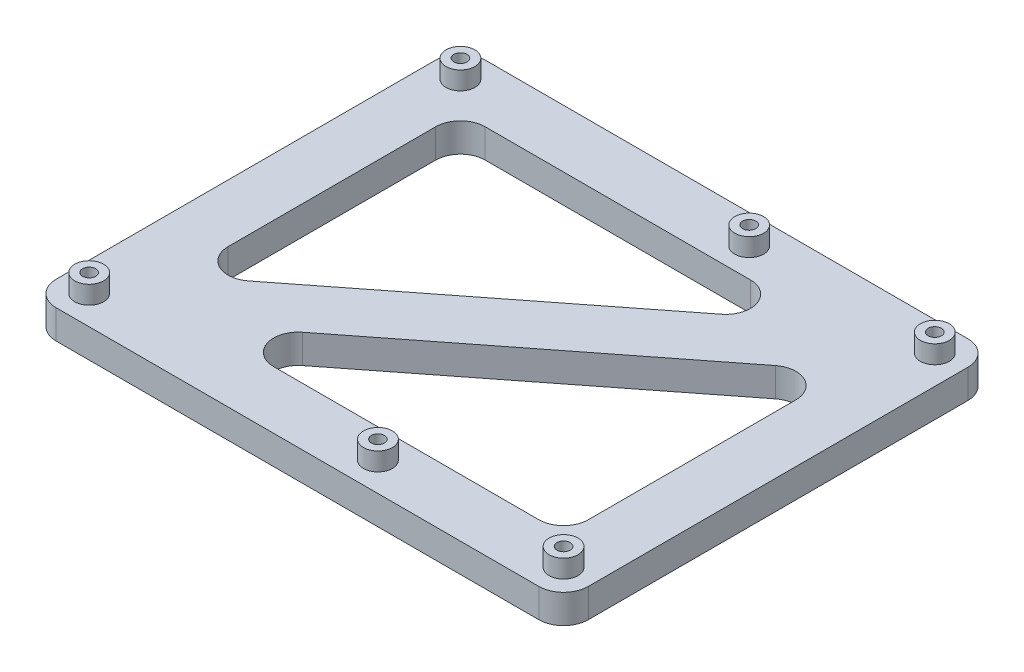
SolidWorks part; units mm, degrees
ref_plane "Front Plane" through (0, 0, 0) normal (0, 0, 1) x (1, 0, 0)
ref_plane "Top Plane" through (0, 0, 0) normal (0, 1, 0) x (1, 0, 0)
ref_plane "Right Plane" through (0, 0, 0) normal (1, 0, 0) x (0, 0, -1)
sketch "Sketch1" plane through (0, 0, 0) normal (0, 1, 0) x (1, 0, 0)
  line L0 (12.5, -45) -> (12.5, 45) construction
  line L1 (57.5, -45) -> (-57.5, -45) construction
  line L2 (57.5, -45) -> (57.5, 45) construction
  line L3 (57.5, 45) -> (-57.5, 45) construction
  line L4 (-57.5, -45) -> (-57.5, 45) construction
  line L5 (57.5, -45) -> (-57.5, 45) construction
  line L6 (57.5, 45) -> (-57.5, -45) construction
  line L7 (-50.5, -30.6329) -> (-50.5, 38)
  line L8 (50.5, 38) -> (48.5556, 38) construction
  line L9 (50.5, -38) -> (50.5, 30.6329)
  line L10 (50.5, -38) -> (-37.1976, -38)
  line L11 (-64.5, -52) -> (-64.5, 52)
  line L12 (64.5, 52) -> (-64.5, 52)
  line L13 (64.5, -52) -> (64.5, 52)
  line L14 (64.5, -52) -> (-64.5, -52)
  line L15 (53.1858, 50.5125) -> (46.142, 45) construction
  line L16 (61.8142, 39.4875) -> (57.5, 36.1112) construction
  line L17 (-57.5, -36.1112) -> (-61.8142, -39.4875) construction
  line L18 (53.1858, 50.5125) -> (-61.8142, -39.4875) construction
  line L19 (-50.5, -30.6329) -> (-57.5, -36.1112) construction
  line L20 (-46.142, -45) -> (-53.1858, -50.5125) construction
  line L21 (61.8142, 39.4875) -> (-53.1858, -50.5125) construction
  line L22 (-37.1976, -38) -> (-46.142, -45) construction
  line L23 (46.142, 45) -> (37.1976, 38) construction
  line L24 (37.1976, 38) -> (-50.5, -30.6329)
  line L25 (57.5, 36.1112) -> (50.5, 30.6329) construction
  line L26 (50.5, 30.6329) -> (-37.1976, -38)
  line L27 (-50.5, -38) -> (-50.5, -30.6329) construction
  line L28 (-50.5, -38) -> (-50.5, 38) construction
  line L29 (-48.5556, -38) -> (-50.5, -38) construction
  line L30 (50.5, -38) -> (-50.5, -38) construction
  line L31 (-37.1976, -38) -> (-48.5556, -38) construction
  line L32 (48.5556, 38) -> (37.1976, 38) construction
  line L33 (37.1976, 38) -> (-50.5, 38)
  line L34 (50.5, 38) -> (-50.5, 38) construction
  line L35 (50.5, 30.6329) -> (50.5, 38) construction
  line L36 (50.5, -38) -> (50.5, 38) construction
  circle A0 centre (12.5, 45) radius 1.6
  circle A1 centre (12.5, -45) radius 1.6
  circle A2 centre (-57.5, 45) radius 1.6
  circle A3 centre (-57.5, -45) radius 1.6
  circle A4 centre (57.5, -45) radius 1.6
  circle A5 centre (57.5, 45) radius 1.6
  circle A6 centre (-57.5, 45) radius 3.5
  circle A7 centre (12.5, 45) radius 3.5
  circle A8 centre (57.5, 45) radius 3.5
  circle A9 centre (-57.5, -45) radius 3.5
  circle A10 centre (12.5, -45) radius 3.5
  circle A11 centre (57.5, -45) radius 3.5
  point P0 (0, 0)
  dimension "D4" = 3.2
  dimension "D9" = 7
  dimension "D1" = 70
  dimension "D2" = 45
  dimension "D3" = 90
  dimension "D5" = 7
  dimension "D6" = 7
  dimension "D7" = 7
  dimension "D8" = 7
extrude "Boss-Extrude1" add sketch "Sketch1" along normal blind 7 contours L14 L13 L12 L11 A11 A10 A9 A8 A7 A6 L33 L24 L7 L26 L9 L10 region at (-0.1343, 0, 0)
fillet "Fillet1" radius 6 10 edges at (-64.5, 3.5, -52) (64.5, 3.5, -52) (64.5, 3.5, 52) (-37.1976, 3.5, 38) (50.5, 3.5, 38) (50.5, 3.5, -30.6329) (-50.5, 3.5, 30.6329) (37.1976, 3.5, -38) (-64.5, 3.5, 52) (-50.5, 3.5, -38)
extrude "Boss-Extrude2" add sketch "Sketch1<3>" along normal blind 11.4 contours A9 A3 | A6 A2 | A7 A0 | A8 A5 | A10 A1 | A11 A4 region at (-60.901, 0, -45) region at (9.099, 0, -45) region at (54.099, 0, -45) region at (-60.901, 0, 45) region at (9.099, 0, 45) region at (54.099, 0, 45)
sketch "Sketch1<3>" plane through (0, 0, 0) normal (0, 1, 0) x (1, 0, 0) same geometry as "Sketch1"
sketch "Sketch2" plane through (0, 0, 0) normal (0, -1, 0) x (1, 0, 0)
  line L1 (-54.3246, 45) -> (-55.9123, 47.75)
  line L2 (-55.9123, 47.75) -> (-59.0877, 47.75)
  line L3 (-59.0877, 47.75) -> (-60.6754, 45)
  line L4 (-60.6754, 45) -> (-59.0877, 42.25)
  line L5 (-59.0877, 42.25) -> (-55.9123, 42.25)
  line L6 (-55.9123, 42.25) -> (-54.3246, 45)
  line L7 (15.6754, 45) -> (14.0877, 47.75)
  line L8 (14.0877, 47.75) -> (10.9123, 47.75)
  line L9 (10.9123, 47.75) -> (9.3246, 45)
  line L10 (9.3246, 45) -> (10.9123, 42.25)
  line L11 (10.9123, 42.25) -> (14.0877, 42.25)
  line L12 (14.0877, 42.25) -> (15.6754, 45)
  line L13 (60.6754, 45) -> (59.0877, 47.75)
  line L14 (59.0877, 47.75) -> (55.9123, 47.75)
  line L15 (55.9123, 47.75) -> (54.3246, 45)
  line L16 (54.3246, 45) -> (55.9123, 42.25)
  line L17 (55.9123, 42.25) -> (59.0877, 42.25)
  line L18 (59.0877, 42.25) -> (60.6754, 45)
  line L19 (-54.3246, -45) -> (-55.9123, -42.25)
  line L20 (-55.9123, -42.25) -> (-59.0877, -42.25)
  line L21 (-59.0877, -42.25) -> (-60.6754, -45)
  line L22 (-60.6754, -45) -> (-59.0877, -47.75)
  line L23 (-59.0877, -47.75) -> (-55.9123, -47.75)
  line L24 (-55.9123, -47.75) -> (-54.3246, -45)
  line L25 (15.6754, -45) -> (14.0877, -42.25)
  line L26 (14.0877, -42.25) -> (10.9123, -42.25)
  line L27 (10.9123, -42.25) -> (9.3246, -45)
  line L28 (9.3246, -45) -> (10.9123, -47.75)
  line L29 (10.9123, -47.75) -> (14.0877, -47.75)
  line L30 (14.0877, -47.75) -> (15.6754, -45)
  line L31 (60.6754, -45) -> (59.0877, -42.25)
  line L32 (59.0877, -42.25) -> (55.9123, -42.25)
  line L33 (55.9123, -42.25) -> (54.3246, -45)
  line L34 (54.3246, -45) -> (55.9123, -47.75)
  line L35 (55.9123, -47.75) -> (59.0877, -47.75)
  line L36 (59.0877, -47.75) -> (60.6754, -45)
  circle A0 centre (12.5, -45) radius 1.6 construction
  circle A1 centre (57.5, -45) radius 1.6 construction
  circle A2 centre (-57.5, -45) radius 1.6 construction
  circle A3 centre (57.5, 45) radius 1.6 construction
  circle A4 centre (12.5, 45) radius 1.6 construction
  circle A5 centre (-57.5, 45) radius 1.6 construction
  circle A6 centre (12.5, -45) radius 1.6
  circle A7 centre (57.5, -45) radius 1.6
  circle A8 centre (-57.5, -45) radius 1.6
  circle A9 centre (57.5, 45) radius 1.6
  circle A10 centre (12.5, 45) radius 1.6
  circle A11 centre (-57.5, 45) radius 1.6
  circle A12 centre (-57.5, 45) radius 2.75 construction
  circle A13 centre (12.5, 45) radius 2.75 construction
  circle A14 centre (57.5, 45) radius 2.75 construction
  circle A15 centre (-57.5, -45) radius 2.75 construction
  circle A16 centre (12.5, -45) radius 2.75 construction
  circle A17 centre (57.5, -45) radius 2.75 construction
  dimension "D1" = 5.5
extrude "Cut-Extrude1" cut sketch "Sketch2" against normal blind 5
